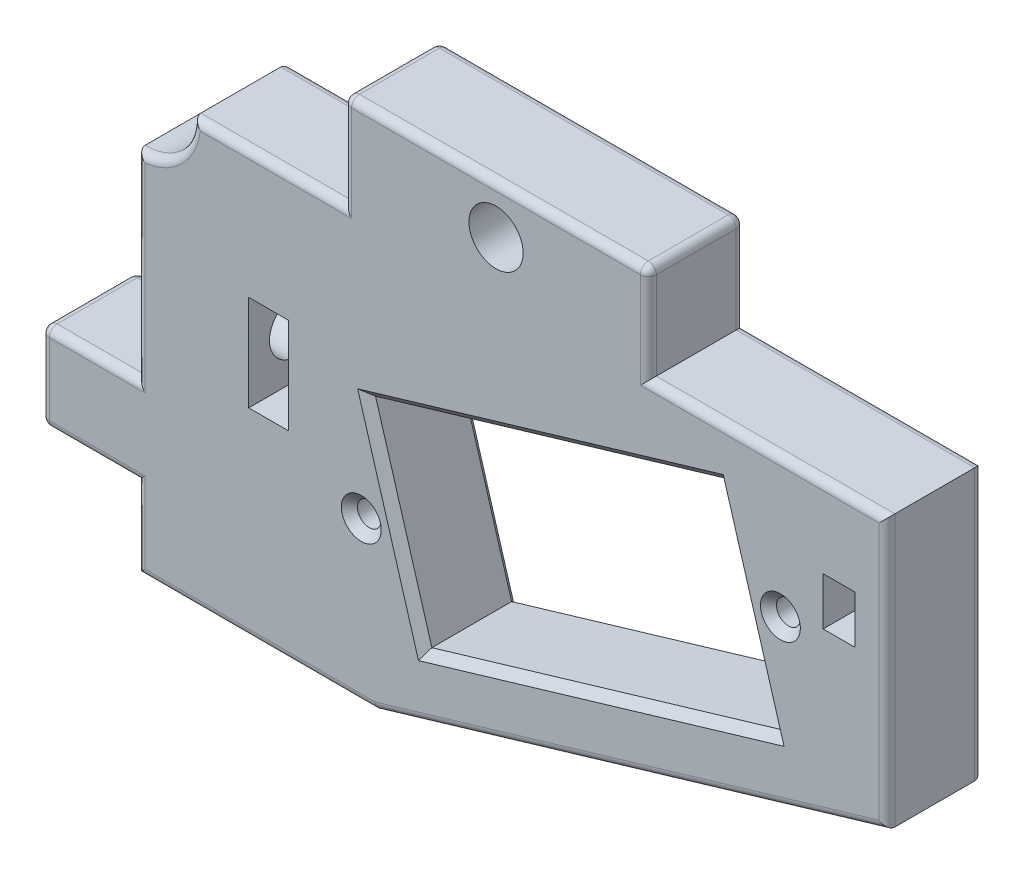
SolidWorks part; units mm, degrees
ref_plane "Front Plane" through (0, 0, 0) normal (0, 0, 1) x (1, 0, 0)
ref_plane "Top Plane" through (0, 0, 0) normal (0, 1, 0) x (1, 0, 0)
ref_plane "Right Plane" through (0, 0, 0) normal (1, 0, 0) x (0, 0, -1)
sketch "Sketch1" plane through (0, 0, 0) normal (0, 0, 1) x (1, 0, 0)
  line L0 (15, -26.5) -> (47, -17)
  line L1 (0, 0) -> (47, 0)
  line L2 (0, 0) -> (0, -26.5)
  line L3 (0, -26.5) -> (47, -26.5)
  line L4 (47, 0) -> (47, -26.5)
  dimension "D1" = 26.5
  dimension "D2" = 47
  dimension "D3" = 15
  dimension "D4" = 17
extrude "Body" add sketch "Sketch1" against normal blind 6 contours L4 L1 L2 L3 L0 region at (21.7161, -11.8484, 0)
sketch "Sketch2" plane through (0, 0, 0) normal (0, 1, 0) x (1, 0, 0)
  line L0 (0, 6) -> (47, 6) construction
  line L1 (0, 0) -> (47, 0) construction
  line L2 (12.95, 6) -> (32.05, 6)
  line L3 (12.95, 6) -> (12.95, 0)
  line L4 (12.95, 0) -> (32.05, 0)
  line L5 (32.05, 6) -> (32.05, 0)
  line L6 (12.35, 0) -> (12.35, 6) construction
  line L7 (32.65, 0) -> (32.65, 6) construction
  dimension "D1" = 0.6
  dimension "D2" = 0.6
extrude "Top Tab" add sketch "Sketch2" along normal blind 6
sketch "Sketch3" plane through (0, 0, 0) normal (-1, 0, 0) x (0, 0, 1)
  line L0 (-6, 0) -> (-6, -26.5) construction
  line L1 (-6, -21.44) -> (0, -21.44)
  line L2 (-6, -21.44) -> (-6, -15.94)
  line L3 (-6, -15.94) -> (0, -15.94)
  line L4 (0, -21.44) -> (0, -15.94)
  line L5 (0, 0) -> (0, -26.5) construction
  line L6 (0, -21.69) -> (-6, -21.69) construction
  line L7 (0, -15.69) -> (-6, -15.69) construction
  dimension "D1" = 0.25
  dimension "D2" = 0.25
extrude "Back Tab" add sketch "Sketch3" along normal blind 6
sketch "Sketch5" plane through (0, 0, 0) normal (-1, 0, 0) x (0, 0, 1)
  circle A0 centre (-3, -11) radius 1.7
  dimension "D1" = 3.4
extrude "Back Screw Hole" cut sketch "Sketch5" against normal blind 12
ref_axis "Axis1" through (12, -11, -3) along (-1, 0, 0)
ref_plane "Plane1" through (0, -11, 0) normal (0, 1, 0) x (1, 0, 0)
sketch "Sketch4" plane through (0, 0, 0) normal (0, 0, 1) x (1, 0, 0)
  line L0 (12.95, 6) -> (32.05, 6) construction
  line L1 (12.95, 6) -> (12.95, 0) construction
  line L2 (17.875, -11) -> (-17.875, -11) construction
  line L3 (7, -8) -> (9.5, -8)
  line L4 (7, -8) -> (7, -14)
  line L5 (7, -14) -> (9.5, -14)
  line L6 (9.5, -8) -> (9.5, -14)
  line L8 (0, 0) -> (0, -15.94) construction
  circle A0 centre (22.5, 3) radius 1.7
  point P4 (22.5, 6)
  point P7 (12.95, 3)
  point P12 (7, -11)
  dimension "D1" = 3.4
  dimension "D2" = 6
  dimension "D3" = 2.5
  dimension "D4" = 7
extrude "Screw and Nut Holes" cut sketch "Sketch4" against normal up to next
sketch "Sketch7" plane through (0, 0, 0) normal (0, 0, 1) x (1, 0, 0)
  circle A0 centre (0, 0) radius 3.5
  dimension "D1" = 7
extrude "Switch Wire Relief" cut sketch "Sketch7" against normal through all
fillet "Fillet1" radius 0.5 32 edges at (32.05, 6, -3) (12.95, 6, -3) (-6, -15.94, -3) (-6, -21.44, -3) (7.5, -26.5, -6) (31, -21.75, -6) (47, -8.5, -6) (22.5, 6, -6) (-6, -18.69, -6) (22.5, 6, 0) (47, -8.5, 0) (31, -21.75, 0) (7.5, -26.5, 0) (-6, -18.69, 0) (2.4749, -2.4749, -6) (2.4749, -2.4749, 0)
sketch "Sketch6" plane through (0, 0, 0) normal (0, 0, 1) x (1, 0, 0)
  line L0 (39.6821, -15.1247) -> (18.1125, -21.5282) construction
  line L1 (18.1125, -21.5282) -> (14.6974, -10.0244) construction
  line L2 (14.6974, -10.0244) -> (36.2669, -3.6209) construction
  line L3 (36.2669, -3.6209) -> (39.6821, -15.1247) construction
  line L4 (14.6974, -9.876) -> (14.6974, -10.0244) construction
  line L5 (36.4017, -3.3723) -> (39.9308, -15.2595)
  line L6 (39.9308, -15.2595) -> (17.9777, -21.7768)
  line L7 (17.9777, -21.7768) -> (14.4487, -9.8896)
  line L8 (14.4487, -9.8896) -> (36.4017, -3.3723)
  circle A0 centre (14.0563, -16.4735) radius 0.75
  circle A1 centre (40.3232, -8.6755) radius 0.75
  dimension "D2" = 1.5
  dimension "D3" = 1.5
  dimension "D1" = 0.2
extrude "Servo Openings" cut sketch "Sketch6" against normal up to next
chamfer "Chamfer1" distance 0.5 angle 45 12 edges at (41.0732, -8.6755, -6) (14.8063, -16.4735, -6) (16.2132, -15.8332, -6) (25.4252, -6.6309, -6) (38.1662, -9.3159, -6) (28.9542, -18.5182, -6) (14.8063, -16.4735, 0) (41.0732, -8.6755, 0) (16.2132, -15.8332, 0) (25.4252, -6.6309, 0) (38.1662, -9.3159, 0) (28.9542, -18.5182, 0)
sketch "Sketch8" plane through (0, 0, 0) normal (0, 0, 1) x (1, 0, 0)
  line L0 (32.05, 0) -> (47, 0) construction
  line L1 (45, -5) -> (43, -5)
  line L2 (45, -5) -> (45, -8)
  line L3 (45, -8) -> (43, -8)
  line L4 (43, -5) -> (43, -8)
  line L5 (47, 0) -> (47, -17) construction
  dimension "D1" = 2
  dimension "D2" = 3
  dimension "D3" = 5
  dimension "D4" = 2
extrude "Cut-Extrude1" cut sketch "Sketch8" against normal through all
